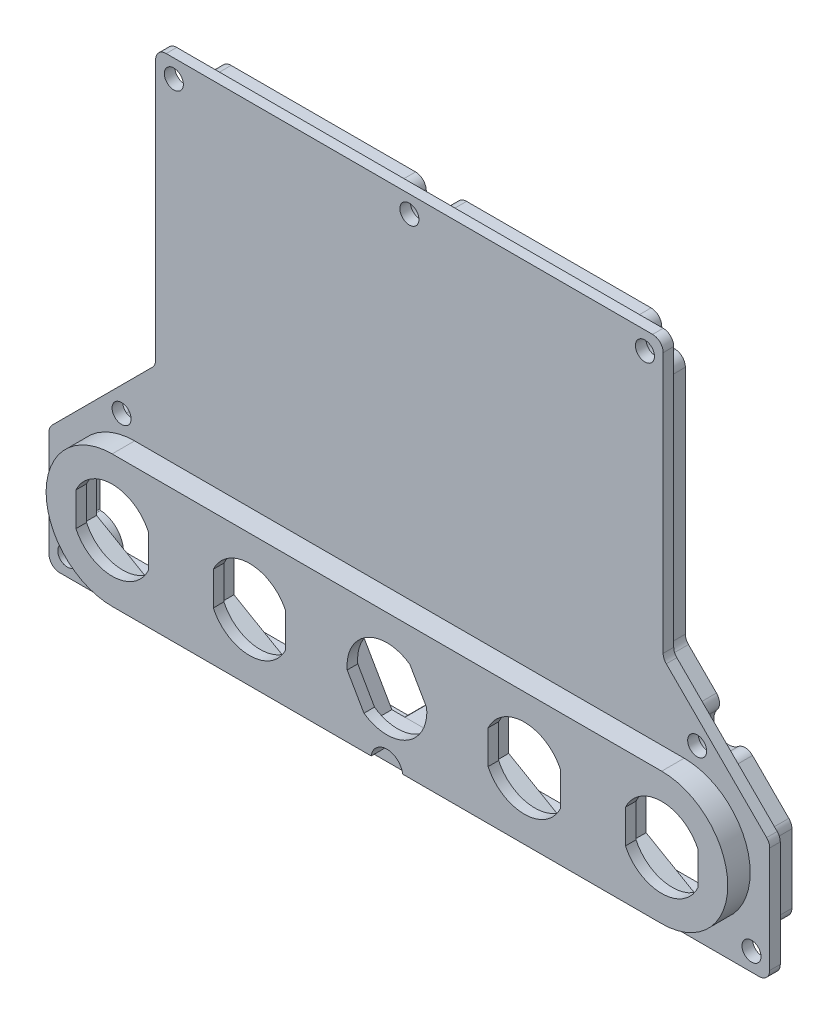
SolidWorks part; units mm, degrees
note: The reader was unsure of these and kept them because the rebuilt part matched: shared geometry of "Sketch1<5>".
ref_plane "Front Plane" through (0, 0, 0) normal (0, 0, 1) x (1, 0, 0)
ref_plane "Top Plane" through (0, 0, 0) normal (0, 1, 0) x (1, 0, 0)
ref_plane "Right Plane" through (0, 0, 0) normal (1, 0, 0) x (0, 0, -1)
sketch "Sketch1" plane through (0, 0, 0) normal (0, 0, 1) x (1, 0, 0)
  line L0 (104.5513, -101.1583) -> (95.5513, -95.9622) construction
  line L1 (113.5513, -95.9622) -> (104.5513, -101.1583) construction
  line L2 (113.5513, -85.5699) -> (113.5513, -95.9622) construction
  line L3 (104.5513, -80.3737) -> (113.5513, -85.5699) construction
  line L4 (95.5513, -85.5699) -> (104.5513, -80.3737) construction
  line L5 (95.5513, -95.9622) -> (95.5513, -85.5699) construction
  line L6 (69.5513, -95.9622) -> (69.5513, -85.5699) construction
  line L7 (78.5513, -101.1583) -> (69.5513, -95.9622) construction
  line L8 (87.5513, -95.9622) -> (78.5513, -101.1583) construction
  line L9 (87.5513, -85.5699) -> (87.5513, -95.9622) construction
  line L10 (78.5513, -80.3737) -> (87.5513, -85.5699) construction
  line L11 (69.5513, -85.5699) -> (78.5513, -80.3737) construction
  line L12 (35.5513, -95.9622) -> (26.5513, -101.1583) construction
  line L13 (26.5513, -101.1583) -> (17.5513, -95.9622) construction
  line L14 (17.5513, -95.9622) -> (17.5513, -85.5699) construction
  line L15 (17.5513, -85.5699) -> (26.5513, -80.3737) construction
  line L16 (26.5513, -80.3737) -> (35.5513, -85.5699) construction
  line L17 (35.5513, -85.5699) -> (35.5513, -95.9622) construction
  line L18 (47.3575, -81.766) -> (57.7498, -81.766) construction
  line L19 (42.1613, -90.766) -> (47.3575, -81.766) construction
  line L20 (47.3575, -99.766) -> (42.1613, -90.766) construction
  line L21 (57.7498, -99.766) -> (47.3575, -99.766) construction
  line L22 (62.946, -90.766) -> (57.7498, -99.766) construction
  line L23 (57.7498, -81.766) -> (62.946, -90.766) construction
  line L24 (9.5513, -95.9622) -> (0.5513, -101.1583) construction
  line L25 (9.5513, -85.5699) -> (9.5513, -95.9622) construction
  line L26 (0.5513, -80.3737) -> (9.5513, -85.5699) construction
  line L27 (-8.4487, -85.5699) -> (0.5513, -80.3737) construction
  line L28 (-8.4487, -95.9622) -> (-8.4487, -85.5699) construction
  line L29 (0.5513, -101.1583) -> (-8.4487, -95.9622) construction
  line L30 (-15.641, -104.9583) -> (-15.641, -84.8874) construction
  line L31 (-15.0552, -83.4732) -> (3.9406, -64.4774) construction
  line L32 (-13.641, -106.9583) -> (118.7436, -106.9583) construction
  line L33 (120.7436, -104.9583) -> (120.7436, -84.8874) construction
  line L34 (120.1579, -83.4732) -> (101.1671, -64.4824) construction
  line L35 (100.5813, -63.0682) -> (100.5813, -13.7887) construction
  line L36 (98.5813, -11.7887) -> (6.5263, -11.7887) construction
  line L37 (4.5263, -63.0632) -> (4.5263, -13.7887) construction
  line L38 (104.5513, -101.1583) -> (95.5513, -95.9622)
  line L39 (113.5513, -95.9622) -> (104.5513, -101.1583)
  line L40 (113.5513, -85.5699) -> (113.5513, -95.9622)
  line L41 (104.5513, -80.3737) -> (113.5513, -85.5699)
  line L42 (95.5513, -85.5699) -> (104.5513, -80.3737)
  line L43 (95.5513, -95.9622) -> (95.5513, -85.5699)
  line L44 (69.5513, -95.9622) -> (69.5513, -85.5699)
  line L45 (78.5513, -101.1583) -> (69.5513, -95.9622)
  line L46 (87.5513, -95.9622) -> (78.5513, -101.1583)
  line L47 (87.5513, -85.5699) -> (87.5513, -95.9622)
  line L48 (78.5513, -80.3737) -> (87.5513, -85.5699)
  line L49 (69.5513, -85.5699) -> (78.5513, -80.3737)
  line L50 (35.5513, -95.9622) -> (26.5513, -101.1583)
  line L51 (26.5513, -101.1583) -> (17.5513, -95.9622)
  line L52 (17.5513, -95.9622) -> (17.5513, -85.5699)
  line L53 (17.5513, -85.5699) -> (26.5513, -80.3737)
  line L54 (26.5513, -80.3737) -> (35.5513, -85.5699)
  line L55 (35.5513, -85.5699) -> (35.5513, -95.9622)
  line L56 (47.3575, -81.766) -> (57.7498, -81.766)
  line L57 (42.1613, -90.766) -> (47.3575, -81.766)
  line L58 (47.3575, -99.766) -> (42.1613, -90.766)
  line L59 (57.7498, -99.766) -> (50.0072, -99.766)
  line L60 (62.946, -90.766) -> (57.7498, -99.766)
  line L61 (57.7498, -81.766) -> (62.946, -90.766)
  line L62 (9.5513, -95.9622) -> (0.5513, -101.1583)
  line L63 (9.5513, -85.5699) -> (9.5513, -95.9622)
  line L64 (0.5513, -80.3737) -> (9.5513, -85.5699)
  line L65 (-8.4487, -85.5699) -> (0.5513, -80.3737)
  line L66 (-8.4487, -95.9622) -> (-8.4487, -85.5699)
  line L67 (0.5513, -101.1583) -> (-8.4487, -95.9622)
  line L68 (-15.641, -104.9583) -> (-15.641, -84.8874)
  line L69 (-15.0552, -83.4732) -> (3.9406, -64.4774)
  line L70 (-13.641, -106.9583) -> (118.7436, -106.9583)
  line L71 (120.7436, -104.9583) -> (120.7436, -84.8874)
  line L72 (120.1579, -83.4732) -> (101.1671, -64.4824)
  line L73 (100.5813, -63.0682) -> (100.5813, -13.7887)
  line L74 (98.5813, -11.7887) -> (6.5263, -11.7887)
  line L75 (4.5263, -63.0632) -> (4.5263, -13.7887)
  line L76 (47.7297, -13.5887) -> (12.8099, -13.5887) construction
  line L77 (6.3263, -63.8088) -> (6.3263, -20.0723) construction
  line L78 (0.4366, -70.5269) -> (5.7406, -65.223) construction
  line L79 (-13.2552, -84.2187) -> (-6.3857, -77.3493) construction
  line L80 (-13.841, -85.633) -> (-13.841, -98.6778) construction
  line L81 (-7.3604, -105.1583) -> (47.7272, -105.1583) construction
  line L82 (57.3755, -105.1583) -> (112.4601, -105.1583) construction
  line L83 (118.9436, -98.6748) -> (118.9436, -85.633) construction
  line L84 (118.3579, -84.2187) -> (111.4884, -77.3493) construction
  line L85 (104.666, -70.5269) -> (99.3671, -65.228) construction
  line L86 (98.7813, -63.8138) -> (98.7813, -20.0723) construction
  line L87 (92.2978, -13.5887) -> (57.378, -13.5887) construction
  line L88 (47.7297, -13.5887) -> (12.8099, -13.5887)
  line L89 (6.3263, -63.8088) -> (6.3263, -20.0723)
  line L90 (0.4366, -70.5269) -> (5.7406, -65.223)
  line L91 (-13.2552, -84.2187) -> (-6.3857, -77.3493)
  line L92 (-13.841, -85.633) -> (-13.841, -98.6778)
  line L93 (-7.3604, -105.1583) -> (47.7272, -105.1583)
  line L94 (57.3755, -105.1583) -> (112.4601, -105.1583)
  line L95 (118.9436, -98.6748) -> (118.9436, -85.633)
  line L96 (118.3579, -84.2187) -> (111.4884, -77.3493)
  line L97 (104.666, -70.5269) -> (99.3671, -65.228)
  line L98 (98.7813, -63.8138) -> (98.7813, -20.0723)
  line L99 (92.2978, -13.5887) -> (57.378, -13.5887)
  line L100 (78.4413, -58.6937) -> (10.3263, -58.6937) construction
  line L101 (78.4413, -34.5887) -> (10.3263, -34.5887) construction
  line L102 (98.7813, -58.6937) -> (6.3263, -58.6937) construction
  line L103 (98.7813, -34.5887) -> (6.3263, -34.5887) construction
  line L104 (96.9813, -34.0887) -> (8.1263, -34.0887)
  line L105 (96.9813, -59.1937) -> (8.1263, -59.1937)
  line L106 (96.9813, -32.2887) -> (8.1263, -32.2887)
  line L107 (96.9813, -60.9937) -> (8.1263, -60.9937)
  line L108 (47.7297, -15.3887) -> (12.8099, -15.3887)
  line L109 (8.1263, -63.8088) -> (8.1263, -60.9937)
  line L110 (1.7094, -71.7997) -> (7.0133, -66.4958)
  line L111 (-11.9824, -85.4915) -> (-5.1129, -78.6221)
  line L112 (-12.041, -85.633) -> (-12.041, -98.6778)
  line L113 (-7.3604, -103.3583) -> (47.7272, -103.3583)
  line L114 (57.3755, -103.3583) -> (112.4601, -103.3583)
  line L115 (117.1436, -98.6748) -> (117.1436, -85.633)
  line L116 (117.0851, -85.4915) -> (110.2156, -78.6221)
  line L117 (103.3932, -71.7997) -> (98.0943, -66.5008)
  line L118 (96.9813, -63.8138) -> (96.9813, -60.9937)
  line L119 (92.2978, -15.3887) -> (57.378, -15.3887)
  line L120 (49.7165, -99.9724) -> (55.3862, -99.9724)
  line L121 (47.3575, -99.766) -> (50.0072, -99.766)
  line L122 (8.1263, -59.1937) -> (8.1263, -34.0887)
  line L123 (98.7813, -59.1937) -> (6.3263, -59.1937) construction
  line L124 (98.7813, -60.9937) -> (6.3263, -60.9937) construction
  line L125 (96.9813, -59.1937) -> (96.9813, -34.0887)
  line L126 (8.1263, -63.8088) -> (8.1263, -20.0723) construction
  line L127 (96.9813, -32.2887) -> (96.9813, -20.0723)
  line L128 (96.9813, -63.8138) -> (96.9813, -20.0723) construction
  line L129 (98.7813, -32.2887) -> (6.3263, -32.2887) construction
  line L130 (8.1263, -32.2887) -> (8.1263, -20.0723)
  line L131 (98.7813, -34.0887) -> (6.3263, -34.0887) construction
  line L132 (9.7513, -85.4544) -> (9.7513, -96.0776)
  line L133 (9.7513, -96.0776) -> (0.5513, -101.3893)
  line L134 (0.5513, -101.3893) -> (-8.6487, -96.0776)
  line L135 (-8.6487, -96.0776) -> (-8.6487, -85.4544)
  line L136 (-8.6487, -85.4544) -> (0.5513, -80.1428)
  line L137 (0.5513, -80.1428) -> (9.7513, -85.4544)
  line L138 (17.3513, -96.0776) -> (17.3513, -85.4544)
  line L139 (17.3513, -85.4544) -> (26.5513, -80.1428)
  line L140 (26.5513, -80.1428) -> (35.7513, -85.4544)
  line L141 (35.7513, -85.4544) -> (35.7513, -96.0776)
  line L142 (35.7513, -96.0776) -> (26.5513, -101.3893)
  line L143 (26.5513, -101.3893) -> (17.3513, -96.0776)
  line L144 (63.1769, -90.766) -> (57.8653, -99.966)
  line L145 (57.8653, -99.966) -> (50.0072, -99.966)
  line L146 (47.242, -99.966) -> (50.0072, -99.966)
  line L147 (47.242, -99.966) -> (41.9304, -90.766)
  line L148 (41.9304, -90.766) -> (47.242, -81.566)
  line L149 (47.242, -81.566) -> (57.8653, -81.566)
  line L150 (57.8653, -81.566) -> (63.1769, -90.766)
  line L151 (69.3513, -96.0776) -> (69.3513, -85.4544)
  line L152 (69.3513, -85.4544) -> (78.5513, -80.1428)
  line L153 (78.5513, -80.1428) -> (87.7513, -85.4544)
  line L154 (87.7513, -85.4544) -> (87.7513, -96.0776)
  line L155 (87.7513, -96.0776) -> (78.5513, -101.3893)
  line L156 (78.5513, -101.3893) -> (69.3513, -96.0776)
  line L157 (113.7513, -85.4544) -> (113.7513, -96.0776)
  line L158 (113.7513, -96.0776) -> (104.5513, -101.3893)
  line L159 (104.5513, -101.3893) -> (95.3513, -96.0776)
  line L160 (95.3513, -96.0776) -> (95.3513, -85.4544)
  line L161 (95.3513, -85.4544) -> (104.5513, -80.1428)
  line L162 (104.5513, -80.1428) -> (113.7513, -85.4544)
  arc A0 (-15.641, -104.9583) -> (-13.641, -106.9583) centre (-13.641, -104.9583) ccw construction
  arc A1 (-15.0552, -83.4732) -> (-15.641, -84.8874) centre (-13.641, -84.8874) ccw construction
  arc A2 (3.9406, -64.4774) -> (4.5263, -63.0632) centre (2.5263, -63.0632) ccw construction
  arc A3 (118.7436, -106.9583) -> (120.7436, -104.9583) centre (118.7436, -104.9583) ccw construction
  arc A4 (120.7436, -84.8874) -> (120.1579, -83.4732) centre (118.7436, -84.8874) ccw construction
  arc A5 (100.5813, -63.0682) -> (101.1671, -64.4824) centre (102.5813, -63.0682) ccw construction
  arc A6 (100.5813, -13.7887) -> (98.5813, -11.7887) centre (98.5813, -13.7887) ccw construction
  arc A7 (6.5263, -11.7887) -> (4.5263, -13.7887) centre (6.5263, -13.7887) ccw construction
  arc A8 (-15.641, -104.9583) -> (-13.641, -106.9583) centre (-13.641, -104.9583) ccw
  arc A9 (-15.0552, -83.4732) -> (-15.641, -84.8874) centre (-13.641, -84.8874) ccw
  arc A10 (3.9406, -64.4774) -> (4.5263, -63.0632) centre (2.5263, -63.0632) ccw
  arc A11 (118.7436, -106.9583) -> (120.7436, -104.9583) centre (118.7436, -104.9583) ccw
  arc A12 (120.7436, -84.8874) -> (120.1579, -83.4732) centre (118.7436, -84.8874) ccw
  arc A13 (100.5813, -63.0682) -> (101.1671, -64.4824) centre (102.5813, -63.0682) ccw
  arc A14 (100.5813, -13.7887) -> (98.5813, -11.7887) centre (98.5813, -13.7887) ccw
  arc A15 (6.5263, -11.7887) -> (4.5263, -13.7887) centre (6.5263, -13.7887) ccw
  circle A16 centre (7.9728, -15.2352) radius 1.8
  circle A17 centre (52.5538, -15.0887) radius 1.8
  circle A18 centre (97.1349, -15.2352) radius 1.8
  circle A19 centre (107.0166, -74.9988) radius 1.8
  circle A20 centre (117.2972, -103.5119) radius 1.8
  circle A21 centre (52.5513, -103.6583) radius 1.8
  circle A22 centre (-12.1957, -103.5131) radius 1.8
  circle A23 centre (-1.9139, -74.9988) radius 1.8
  arc A24 (57.378, -13.5887) -> (55.3887, -15.3825) centre (57.378, -15.5887) ccw construction
  arc A25 (49.719, -15.3825) -> (55.3887, -15.3825) centre (52.5538, -15.0887) ccw construction
  arc A26 (49.719, -15.3825) -> (47.7297, -13.5887) centre (47.7297, -15.5887) ccw construction
  arc A27 (12.8099, -13.5887) -> (10.8152, -15.4429) centre (12.8099, -15.5887) ccw construction
  arc A28 (8.1805, -18.0776) -> (10.8152, -15.4429) centre (7.9728, -15.2352) ccw construction
  arc A29 (8.1805, -18.0776) -> (6.3263, -20.0723) centre (8.3263, -20.0723) ccw construction
  arc A30 (5.7406, -65.223) -> (6.3263, -63.8088) centre (4.3263, -63.8088) ccw construction
  arc A31 (0.4366, -70.5269) -> (0.2984, -73.202) centre (1.8509, -71.9411) ccw construction
  arc A32 (-3.7106, -77.211) -> (0.2984, -73.202) centre (-1.9139, -74.9988) ccw construction
  arc A33 (-3.7106, -77.211) -> (-6.3857, -77.3493) centre (-4.9715, -78.7635) ccw construction
  arc A34 (-13.2552, -84.2187) -> (-13.841, -85.633) centre (-11.841, -85.633) ccw construction
  arc A35 (-13.841, -98.6778) -> (-11.9873, -100.6724) centre (-11.841, -98.6778) ccw construction
  arc A36 (-9.355, -103.3047) -> (-11.9873, -100.6724) centre (-12.1957, -103.5131) ccw construction
  arc A37 (-9.355, -103.3047) -> (-7.3604, -105.1583) centre (-7.3604, -103.1583) ccw construction
  arc A38 (47.7272, -105.1583) -> (49.7165, -103.3645) centre (47.7272, -103.1583) ccw construction
  arc A39 (55.3862, -103.3645) -> (49.7165, -103.3645) centre (52.5513, -103.6583) ccw construction
  arc A40 (55.3862, -103.3645) -> (57.3755, -105.1583) centre (57.3755, -103.1583) ccw construction
  arc A41 (112.4601, -105.1583) -> (114.4548, -103.3041) centre (112.4601, -103.1583) ccw construction
  arc A42 (117.0894, -100.6695) -> (114.4548, -103.3041) centre (117.2972, -103.5119) ccw construction
  arc A43 (117.0894, -100.6695) -> (118.9436, -98.6748) centre (116.9436, -98.6748) ccw construction
  arc A44 (118.9436, -85.633) -> (118.3579, -84.2187) centre (116.9436, -85.633) ccw construction
  arc A45 (111.4884, -77.3493) -> (108.8133, -77.211) centre (110.0742, -78.7635) ccw construction
  arc A46 (104.8043, -73.202) -> (108.8133, -77.211) centre (107.0166, -74.9988) ccw construction
  arc A47 (104.8043, -73.202) -> (104.666, -70.5269) centre (103.2518, -71.9411) ccw construction
  arc A48 (98.7813, -63.8138) -> (99.3671, -65.228) centre (100.7813, -63.8138) ccw construction
  arc A49 (94.2925, -15.4429) -> (92.2978, -13.5887) centre (92.2978, -15.5887) ccw construction
  arc A50 (94.2925, -15.4429) -> (96.9271, -18.0776) centre (97.1349, -15.2352) ccw construction
  arc A51 (98.7813, -20.0723) -> (96.9271, -18.0776) centre (96.7813, -20.0723) ccw construction
  arc A52 (57.378, -13.5887) -> (55.3887, -15.3825) centre (57.378, -15.5887) ccw
  arc A53 (49.719, -15.3825) -> (55.3887, -15.3825) centre (52.5538, -15.0887) ccw
  arc A54 (49.719, -15.3825) -> (47.7297, -13.5887) centre (47.7297, -15.5887) ccw
  arc A55 (12.8099, -13.5887) -> (10.8152, -15.4429) centre (12.8099, -15.5887) ccw
  arc A56 (8.1805, -18.0776) -> (10.8152, -15.4429) centre (7.9728, -15.2352) ccw
  arc A57 (8.1805, -18.0776) -> (6.3263, -20.0723) centre (8.3263, -20.0723) ccw
  arc A58 (5.7406, -65.223) -> (6.3263, -63.8088) centre (4.3263, -63.8088) ccw
  arc A59 (0.4366, -70.5269) -> (0.2984, -73.202) centre (1.8509, -71.9411) ccw
  arc A60 (-3.7106, -77.211) -> (0.2984, -73.202) centre (-1.9139, -74.9988) ccw
  arc A61 (-3.7106, -77.211) -> (-6.3857, -77.3493) centre (-4.9715, -78.7635) ccw
  arc A62 (-13.2552, -84.2187) -> (-13.841, -85.633) centre (-11.841, -85.633) ccw
  arc A63 (-13.841, -98.6778) -> (-11.9873, -100.6724) centre (-11.841, -98.6778) ccw
  arc A64 (-9.355, -103.3047) -> (-11.9873, -100.6724) centre (-12.1957, -103.5131) ccw
  arc A65 (-9.355, -103.3047) -> (-7.3604, -105.1583) centre (-7.3604, -103.1583) ccw
  arc A66 (47.7272, -105.1583) -> (49.7165, -103.3645) centre (47.7272, -103.1583) ccw
  arc A67 (55.3862, -103.3645) -> (49.7165, -103.3645) centre (52.5513, -103.6583) ccw
  arc A68 (55.3862, -103.3645) -> (57.3755, -105.1583) centre (57.3755, -103.1583) ccw
  arc A69 (112.4601, -105.1583) -> (114.4548, -103.3041) centre (112.4601, -103.1583) ccw
  arc A70 (117.0894, -100.6695) -> (114.4548, -103.3041) centre (117.2972, -103.5119) ccw
  arc A71 (117.0894, -100.6695) -> (118.9436, -98.6748) centre (116.9436, -98.6748) ccw
  arc A72 (118.9436, -85.633) -> (118.3579, -84.2187) centre (116.9436, -85.633) ccw
  arc A73 (111.4884, -77.3493) -> (108.8133, -77.211) centre (110.0742, -78.7635) ccw
  arc A74 (104.8043, -73.202) -> (108.8133, -77.211) centre (107.0166, -74.9988) ccw
  arc A75 (104.8043, -73.202) -> (104.666, -70.5269) centre (103.2518, -71.9411) ccw
  arc A76 (98.7813, -63.8138) -> (99.3671, -65.228) centre (100.7813, -63.8138) ccw
  arc A77 (94.2925, -15.4429) -> (92.2978, -13.5887) centre (92.2978, -15.5887) ccw
  arc A78 (94.2925, -15.4429) -> (96.9271, -18.0776) centre (97.1349, -15.2352) ccw
  arc A79 (98.7813, -20.0723) -> (96.9271, -18.0776) centre (96.7813, -20.0723) ccw
  arc A80 (12.8099, -15.3887) -> (12.6104, -15.5741) centre (12.8099, -15.5887) ccw
  arc A81 (8.3118, -19.8728) -> (12.6104, -15.5741) centre (7.9728, -15.2352) ccw
  arc A82 (8.3118, -19.8728) -> (8.1263, -20.0723) centre (8.3263, -20.0723) ccw
  arc A83 (7.0133, -66.4958) -> (8.1263, -63.8088) centre (4.3263, -63.8088) ccw
  arc A84 (1.7094, -71.7997) -> (1.6956, -72.0672) centre (1.8509, -71.9411) ccw
  arc A85 (-4.8454, -78.6083) -> (1.6956, -72.0672) centre (-1.9139, -74.9988) ccw
  arc A86 (-4.8454, -78.6083) -> (-5.1129, -78.6221) centre (-4.9715, -78.7635) ccw
  arc A87 (-11.9824, -85.4915) -> (-12.041, -85.633) centre (-11.841, -85.633) ccw
  arc A88 (-12.041, -98.6778) -> (-11.8556, -98.8772) centre (-11.841, -98.6778) ccw
  arc A89 (-7.5599, -103.173) -> (-11.8556, -98.8772) centre (-12.1957, -103.5131) ccw
  arc A90 (-7.5599, -103.173) -> (-7.3604, -103.3583) centre (-7.3604, -103.1583) ccw
  arc A91 (47.7272, -103.3583) -> (47.9261, -103.1789) centre (47.7272, -103.1583) ccw
  arc A92 (57.1766, -103.1789) -> (55.3862, -99.9724) centre (52.5513, -103.6583) ccw
  arc A93 (57.1766, -103.1789) -> (57.3755, -103.3583) centre (57.3755, -103.1583) ccw
  arc A94 (112.4601, -103.3583) -> (112.6596, -103.1729) centre (112.4601, -103.1583) ccw
  arc A95 (116.9582, -98.8742) -> (112.6596, -103.1729) centre (117.2972, -103.5119) ccw
  arc A96 (116.9582, -98.8742) -> (117.1436, -98.6748) centre (116.9436, -98.6748) ccw
  arc A97 (117.1436, -85.633) -> (117.0851, -85.4915) centre (116.9436, -85.633) ccw
  arc A98 (110.2156, -78.6221) -> (109.9481, -78.6083) centre (110.0742, -78.7635) ccw
  arc A99 (103.4071, -72.0672) -> (109.9481, -78.6083) centre (107.0166, -74.9988) ccw
  arc A100 (103.4071, -72.0672) -> (103.3932, -71.7997) centre (103.2518, -71.9411) ccw
  arc A101 (96.9813, -63.8138) -> (98.0943, -66.5008) centre (100.7813, -63.8138) ccw
  arc A102 (96.9813, -20.0723) -> (96.7959, -19.8728) centre (96.7813, -20.0723) ccw
  arc A103 (92.4973, -15.5741) -> (96.7959, -19.8728) centre (97.1349, -15.2352) ccw
  arc A104 (92.4973, -15.5741) -> (92.2978, -15.3887) centre (92.2978, -15.5887) ccw
  arc A105 (57.378, -15.3887) -> (57.1791, -15.5681) centre (57.378, -15.5887) ccw
  arc A106 (47.9286, -15.5681) -> (57.1791, -15.5681) centre (52.5538, -15.0887) ccw
  arc A107 (47.9286, -15.5681) -> (47.7297, -15.3887) centre (47.7297, -15.5887) ccw
  arc A108 (49.7165, -99.9724) -> (47.9261, -103.1789) centre (52.5513, -103.6583) ccw
  arc A110 (57.1766, -103.1789) -> (47.9261, -103.1789) centre (52.5513, -103.6583) ccw construction
  dimension "D1" = 0.5
  dimension "D2" = 0.5
  dimension "D3" = 1.8
  dimension "D4" = 1.8
  dimension "D5" = 1.8
  dimension "D6" = 0.2
extrude "Boss-Extrude1" add sketch "Sketch1" against normal blind 4 contours L98 A79 A78 A77 L99 A52 A53 A54 L88 A55 A56 A57 L89 A58 L90 A59 A60 A61 L91 A62 L92 A63 A64 A65 L93 A66 A67 A68 L94 A69 A70 A71 L95 A72 L96 A73 A74 A75 L97 A76 L125 L105 L122 L104 A107 A106 A105 L119 A104
extrude "Boss-Extrude3" add sketch "Sketch1<5>" along normal blind 2 contours L98 A79 A78 A77 L99 A52 A53 A54 L88 A55 A56 A57 L89 A58 L90 A59 A60 A61 L91 A62 L92 A63 A64 A65 L93 A66 A67 A68 L94 A69 A70 A71 L95 A72 L96 A73 A74 A75 L97 A76 L125 L105 L122 L104 A107 A106 A105 L119 A104 | L74 A15 L75 A10 L69 A9 L68 A8 L70 A11 L71 A12 L72 A13 L73 A14 A79 L98 A76 L97 A75 A74 A73 L96 A72 L95 A71 A70 A69 L94 A68 A67 A66 L93 A65 A64 A63 L92 A62 L91 A61 A60 A59 L90 A58 L89 A57 A56 A55 L88 | A108 L120 A92 A93 L114 A94 A95 A96 L115 A97 L116 A98 A99 A100 L117 A101 L118 L107 L109 A83 L110 A84 A85 A86 L111 A87 L112 A88 A89 A90 L113 A91 L121 L58 L57 L56 L61 L60 L59 L38 L43 L42 L41 L40 L39 L44 L49 L48 | L105 L125 L104 L122 | A106 A107 L108 A80 A81 A82 L130 L106 L127 A102 A103 A104 L119 A105
sketch "Sketch1<5>" plane through (0, 0, 0) normal (0, 0, 1) x (1, 0, 0) same geometry as "Sketch1"
sketch "Sketch2" plane through (0, 0, 2) normal (0, 0, 1) x (1, 0, 0)
  line L0 (0.5513, -78.266) -> (104.5513, -78.266)
  line L1 (0.5513, -103.266) -> (49.5771, -103.266)
  line L2 (55.5256, -103.266) -> (104.5513, -103.266)
  line L3 (-8.6487, -85.4544) -> (0.5513, -80.1428) construction
  line L4 (-8.6487, -85.4544) -> (0.5513, -80.1428)
  line L5 (113.7513, -96.0776) -> (104.5513, -101.3893) construction
  line L6 (113.7513, -85.4544) -> (113.7513, -96.0776) construction
  line L7 (104.5513, -80.1428) -> (113.7513, -85.4544) construction
  line L8 (104.5513, -101.3893) -> (95.3513, -96.0776) construction
  line L9 (95.3513, -96.0776) -> (95.3513, -85.4544) construction
  line L10 (95.3513, -85.4544) -> (104.5513, -80.1428) construction
  line L11 (87.7513, -96.0776) -> (78.5513, -101.3893) construction
  line L12 (87.7513, -85.4544) -> (87.7513, -96.0776) construction
  line L13 (78.5513, -80.1428) -> (87.7513, -85.4544) construction
  line L14 (78.5513, -101.3893) -> (69.3513, -96.0776) construction
  line L15 (69.3513, -85.4544) -> (78.5513, -80.1428) construction
  line L16 (69.3513, -96.0776) -> (69.3513, -85.4544) construction
  line L17 (47.242, -81.566) -> (57.8653, -81.566) construction
  line L18 (57.8653, -81.566) -> (63.1769, -90.766) construction
  line L19 (63.1769, -90.766) -> (57.8653, -99.966) construction
  line L20 (57.8653, -99.966) -> (47.242, -99.966) construction
  line L21 (47.242, -99.966) -> (41.9304, -90.766) construction
  line L22 (41.9304, -90.766) -> (47.242, -81.566) construction
  line L23 (26.5513, -80.1428) -> (35.7513, -85.4544) construction
  line L24 (35.7513, -85.4544) -> (35.7513, -96.0776) construction
  line L25 (35.7513, -96.0776) -> (26.5513, -101.3893) construction
  line L26 (26.5513, -101.3893) -> (17.3513, -96.0776) construction
  line L27 (17.3513, -96.0776) -> (17.3513, -85.4544) construction
  line L28 (17.3513, -85.4544) -> (26.5513, -80.1428) construction
  line L29 (0.5513, -80.1428) -> (9.7513, -85.4544) construction
  line L30 (9.7513, -85.4544) -> (9.7513, -96.0776) construction
  line L31 (9.7513, -96.0776) -> (0.5513, -101.3893) construction
  line L32 (0.5513, -101.3893) -> (-8.6487, -96.0776) construction
  line L33 (-8.6487, -96.0776) -> (-8.6487, -85.4544) construction
  line L34 (113.7513, -96.0776) -> (104.5513, -101.3893)
  line L35 (113.7513, -85.4544) -> (113.7513, -96.0776)
  line L36 (104.5513, -80.1428) -> (113.7513, -85.4544)
  line L37 (104.5513, -101.3893) -> (95.3513, -96.0776)
  line L38 (95.3513, -96.0776) -> (95.3513, -85.4544)
  line L39 (95.3513, -85.4544) -> (104.5513, -80.1428)
  line L40 (87.7513, -96.0776) -> (78.5513, -101.3893)
  line L41 (87.7513, -85.4544) -> (87.7513, -96.0776)
  line L42 (78.5513, -80.1428) -> (87.7513, -85.4544)
  line L43 (78.5513, -101.3893) -> (69.3513, -96.0776)
  line L44 (69.3513, -85.4544) -> (78.5513, -80.1428)
  line L45 (69.3513, -96.0776) -> (69.3513, -85.4544)
  line L46 (47.242, -81.566) -> (57.8653, -81.566)
  line L47 (57.8653, -81.566) -> (63.1769, -90.766)
  line L48 (63.1769, -90.766) -> (57.8653, -99.966)
  line L49 (57.8653, -99.966) -> (47.242, -99.966)
  line L50 (47.242, -99.966) -> (41.9304, -90.766)
  line L51 (41.9304, -90.766) -> (47.242, -81.566)
  line L52 (26.5513, -80.1428) -> (35.7513, -85.4544)
  line L53 (35.7513, -85.4544) -> (35.7513, -96.0776)
  line L54 (35.7513, -96.0776) -> (26.5513, -101.3893)
  line L55 (26.5513, -101.3893) -> (17.3513, -96.0776)
  line L56 (17.3513, -96.0776) -> (17.3513, -85.4544)
  line L57 (17.3513, -85.4544) -> (26.5513, -80.1428)
  line L58 (0.5513, -80.1428) -> (9.7513, -85.4544)
  line L59 (9.7513, -85.4544) -> (9.7513, -96.0776)
  line L60 (9.7513, -96.0776) -> (0.5513, -101.3893)
  line L61 (0.5513, -101.3893) -> (-8.6487, -96.0776)
  line L62 (-8.6487, -96.0776) -> (-8.6487, -85.4544)
  arc A0 (0.5513, -78.266) -> (0.5513, -103.266) centre (0.5513, -90.766) ccw
  arc A1 (104.5513, -103.266) -> (104.5513, -78.266) centre (104.5513, -90.766) ccw
  arc A2 (55.5256, -103.266) -> (49.5771, -103.266) centre (52.5513, -103.6583) ccw
extrude "Boss-Extrude4" add sketch "Sketch2" along normal blind 2.25 contours A2 L2 A1 L0 A0 L1 L38 L39 L36 L35 L34 L37 L43 L45 L44 L42 L41 L40 L50 L51 L46 L47 L48 L49 L56 L57 L52 L53 L54 L55 L61 L62 L4 L58 L59 L60
sketch "Sketch3" plane through (0, 0, 4.25) normal (0, 0, 1) x (1, 0, 0)
  line L0 (33.3013, -90.766) -> (33.3013, -93.9188) construction
  line L1 (7.3013, -90.766) -> (7.3013, -93.9188) construction
  line L2 (-6.1987, -90.766) -> (-6.1987, -93.9188) construction
  line L3 (19.8013, -90.766) -> (19.8013, -93.9188) construction
  line L4 (19.8013, -90.766) -> (19.8013, -87.6132) construction
  line L5 (33.3013, -90.766) -> (33.3013, -87.6132) construction
  line L6 (7.3013, -90.766) -> (7.3013, -87.6132) construction
  line L7 (-6.1987, -90.766) -> (-6.1987, -87.6132) construction
  line L8 (33.3013, -90.766) -> (33.3013, -93.9188)
  line L9 (7.3013, -90.766) -> (7.3013, -93.9188)
  line L10 (-6.1987, -90.766) -> (-6.1987, -93.9188)
  line L11 (19.8013, -90.766) -> (19.8013, -93.9188)
  line L12 (19.8013, -90.766) -> (19.8013, -87.6132)
  line L13 (33.3013, -90.766) -> (33.3013, -87.6132)
  line L14 (7.3013, -90.766) -> (7.3013, -87.6132)
  line L15 (-6.1987, -90.766) -> (-6.1987, -87.6132)
  line L16 (97.8013, -90.766) -> (97.8013, -93.9188) construction
  line L17 (97.8013, -90.766) -> (97.8013, -87.6132) construction
  line L18 (111.3013, -90.766) -> (111.3013, -93.9188) construction
  line L19 (111.3013, -90.766) -> (111.3013, -87.6132) construction
  line L20 (85.3013, -90.766) -> (85.3013, -93.9188) construction
  line L21 (85.3013, -90.766) -> (85.3013, -87.6132) construction
  line L22 (71.8013, -90.766) -> (71.8013, -93.9188) construction
  line L23 (71.8013, -90.766) -> (71.8013, -87.6132) construction
  line L24 (46.708, -94.141) -> (48.2844, -96.8714) construction
  line L25 (46.708, -94.141) -> (45.1316, -91.4106) construction
  line L26 (58.3993, -87.391) -> (59.9757, -90.1214) construction
  line L27 (58.3993, -87.391) -> (56.8229, -84.6606) construction
  line L28 (97.8013, -90.766) -> (97.8013, -93.9188)
  line L29 (97.8013, -90.766) -> (97.8013, -87.6132)
  line L30 (111.3013, -90.766) -> (111.3013, -93.9188)
  line L31 (111.3013, -90.766) -> (111.3013, -87.6132)
  line L32 (85.3013, -90.766) -> (85.3013, -93.9188)
  line L33 (85.3013, -90.766) -> (85.3013, -87.6132)
  line L34 (71.8013, -90.766) -> (71.8013, -93.9188)
  line L35 (71.8013, -90.766) -> (71.8013, -87.6132)
  line L36 (46.708, -94.141) -> (48.2844, -96.8714)
  line L37 (46.708, -94.141) -> (45.1316, -91.4106)
  line L38 (58.3993, -87.391) -> (59.9757, -90.1214)
  line L39 (58.3993, -87.391) -> (56.8229, -84.6606)
  line L40 (7.4013, -90.766) -> (7.4013, -93.9409)
  line L41 (7.4013, -90.766) -> (7.4013, -87.5911)
  line L42 (-6.2987, -90.766) -> (-6.2987, -87.5911)
  line L43 (-6.2987, -90.766) -> (-6.2987, -93.9409)
  line L44 (33.4013, -90.766) -> (33.4013, -93.9409)
  line L45 (33.4013, -90.766) -> (33.4013, -87.5911)
  line L46 (19.7013, -90.766) -> (19.7013, -87.5911)
  line L47 (19.7013, -90.766) -> (19.7013, -93.9409)
  line L48 (46.6214, -94.191) -> (45.0339, -91.4415)
  line L49 (46.6214, -94.191) -> (48.2088, -96.9406)
  line L50 (58.4859, -87.341) -> (60.0734, -90.0906)
  line L51 (58.4859, -87.341) -> (56.8985, -84.5915)
  line L52 (85.4013, -90.766) -> (85.4013, -93.9409)
  line L53 (85.4013, -90.766) -> (85.4013, -87.5911)
  line L54 (71.7013, -90.766) -> (71.7013, -87.5911)
  line L55 (71.7013, -90.766) -> (71.7013, -93.9409)
  line L56 (111.4013, -90.766) -> (111.4013, -93.9409)
  line L57 (111.4013, -90.766) -> (111.4013, -87.5911)
  line L58 (97.7013, -90.766) -> (97.7013, -87.5911)
  line L59 (97.7013, -90.766) -> (97.7013, -93.9409)
  line L60 (55.5256, -103.266) -> (104.5513, -103.266) construction
  line L61 (0.5513, -78.266) -> (104.5513, -78.266) construction
  line L62 (0.5513, -103.266) -> (49.5771, -103.266) construction
  line L63 (55.5256, -103.266) -> (104.5513, -103.266)
  line L64 (0.5513, -78.266) -> (104.5513, -78.266)
  line L65 (0.5513, -103.266) -> (49.5771, -103.266)
  arc A0 (-6.1987, -93.9188) -> (7.3013, -93.9188) centre (0.5513, -90.766) ccw construction
  arc A1 (19.8013, -93.9188) -> (33.3013, -93.9188) centre (26.5513, -90.766) ccw construction
  arc A2 (33.3013, -87.6132) -> (19.8013, -87.6132) centre (26.5513, -90.766) ccw construction
  arc A3 (7.3013, -87.6132) -> (-6.1987, -87.6132) centre (0.5513, -90.766) ccw construction
  arc A4 (-6.1987, -93.9188) -> (7.3013, -93.9188) centre (0.5513, -90.766) ccw
  arc A5 (19.8013, -93.9188) -> (33.3013, -93.9188) centre (26.5513, -90.766) ccw
  arc A6 (33.3013, -87.6132) -> (19.8013, -87.6132) centre (26.5513, -90.766) ccw
  arc A7 (7.3013, -87.6132) -> (-6.1987, -87.6132) centre (0.5513, -90.766) ccw
  arc A8 (97.8013, -93.9188) -> (111.3013, -93.9188) centre (104.5513, -90.766) ccw construction
  arc A9 (111.3013, -87.6132) -> (97.8013, -87.6132) centre (104.5513, -90.766) ccw construction
  arc A10 (71.8013, -93.9188) -> (85.3013, -93.9188) centre (78.5513, -90.766) ccw construction
  arc A11 (85.3013, -87.6132) -> (71.8013, -87.6132) centre (78.5513, -90.766) ccw construction
  arc A12 (56.8229, -84.6606) -> (45.1316, -91.4106) centre (52.5536, -90.766) ccw construction
  arc A13 (48.2844, -96.8714) -> (59.9757, -90.1214) centre (52.5536, -90.766) ccw construction
  arc A14 (97.8013, -93.9188) -> (111.3013, -93.9188) centre (104.5513, -90.766) ccw
  arc A15 (111.3013, -87.6132) -> (97.8013, -87.6132) centre (104.5513, -90.766) ccw
  arc A16 (71.8013, -93.9188) -> (85.3013, -93.9188) centre (78.5513, -90.766) ccw
  arc A17 (85.3013, -87.6132) -> (71.8013, -87.6132) centre (78.5513, -90.766) ccw
  arc A18 (56.8229, -84.6606) -> (45.1316, -91.4106) centre (52.5536, -90.766) ccw
  arc A19 (48.2844, -96.8714) -> (59.9757, -90.1214) centre (52.5536, -90.766) ccw
  arc A20 (-6.2987, -93.9409) -> (7.4013, -93.9409) centre (0.5513, -90.766) ccw
  arc A21 (7.4013, -87.5911) -> (-6.2987, -87.5911) centre (0.5513, -90.766) ccw
  arc A22 (19.7013, -93.9409) -> (33.4013, -93.9409) centre (26.5513, -90.766) ccw
  arc A23 (33.4013, -87.5911) -> (19.7013, -87.5911) centre (26.5513, -90.766) ccw
  arc A24 (56.8985, -84.5915) -> (45.0339, -91.4415) centre (52.5536, -90.766) ccw
  arc A25 (48.2088, -96.9406) -> (60.0734, -90.0906) centre (52.5536, -90.766) ccw
  arc A26 (71.7013, -93.9409) -> (85.4013, -93.9409) centre (78.5513, -90.766) ccw
  arc A27 (85.4013, -87.5911) -> (71.7013, -87.5911) centre (78.5513, -90.766) ccw
  arc A28 (97.7013, -93.9409) -> (111.4013, -93.9409) centre (104.5513, -90.766) ccw
  arc A29 (111.4013, -87.5911) -> (97.7013, -87.5911) centre (104.5513, -90.766) ccw
  arc A30 (104.5513, -103.266) -> (104.5513, -78.266) centre (104.5513, -90.766) ccw construction
  arc A31 (55.5256, -103.266) -> (49.5771, -103.266) centre (52.5513, -103.6583) ccw construction
  arc A32 (0.5513, -78.266) -> (0.5513, -103.266) centre (0.5513, -90.766) ccw construction
  arc A33 (104.5513, -103.266) -> (104.5513, -78.266) centre (104.5513, -90.766) ccw
  arc A34 (55.5256, -103.266) -> (49.5771, -103.266) centre (52.5513, -103.6583) ccw
  arc A35 (0.5513, -78.266) -> (0.5513, -103.266) centre (0.5513, -90.766) ccw
  arc M1 (49.5771, -103.266) -> (55.5256, -103.266) centre (52.5513, -103.6583) cw
  line M2 (55.5256, -103.266) -> (104.5513, -103.266)
  arc M3 (104.5513, -103.266) -> (104.5513, -78.266) centre (104.5513, -90.766) ccw
  line M4 (104.5513, -78.266) -> (0.5513, -78.266)
  arc M5 (0.5513, -78.266) -> (0.5513, -103.266) centre (0.5513, -90.766) ccw
  line M6 (0.5513, -103.266) -> (49.5771, -103.266)
  line M7 (95.3513, -96.0776) -> (95.3513, -85.4544)
  line M8 (95.3513, -85.4544) -> (104.5513, -80.1428)
  line M9 (104.5513, -80.1428) -> (113.7513, -85.4544)
  line M10 (113.7513, -85.4544) -> (113.7513, -96.0776)
  line M11 (113.7513, -96.0776) -> (104.5513, -101.3893)
  line M12 (104.5513, -101.3893) -> (95.3513, -96.0776)
  line M13 (78.5513, -101.3893) -> (69.3513, -96.0776)
  line M14 (69.3513, -96.0776) -> (69.3513, -85.4544)
  line M15 (69.3513, -85.4544) -> (78.5513, -80.1428)
  line M16 (78.5513, -80.1428) -> (87.7513, -85.4544)
  line M17 (87.7513, -85.4544) -> (87.7513, -96.0776)
  line M18 (87.7513, -96.0776) -> (78.5513, -101.3893)
  line M19 (47.242, -99.966) -> (41.9304, -90.766)
  line M20 (41.9304, -90.766) -> (47.242, -81.566)
  line M21 (47.242, -81.566) -> (57.8653, -81.566)
  line M22 (57.8653, -81.566) -> (63.1769, -90.766)
  line M23 (63.1769, -90.766) -> (57.8653, -99.966)
  line M24 (57.8653, -99.966) -> (47.242, -99.966)
  line M25 (17.3513, -96.0776) -> (17.3513, -85.4544)
  line M26 (17.3513, -85.4544) -> (26.5513, -80.1428)
  line M27 (26.5513, -80.1428) -> (35.7513, -85.4544)
  line M28 (35.7513, -85.4544) -> (35.7513, -96.0776)
  line M29 (35.7513, -96.0776) -> (26.5513, -101.3893)
  line M30 (26.5513, -101.3893) -> (17.3513, -96.0776)
  line M31 (0.5513, -101.3893) -> (-8.6487, -96.0776)
  line M32 (-8.6487, -96.0776) -> (-8.6487, -85.4544)
  line M33 (-8.6487, -85.4544) -> (0.5513, -80.1428)
  line M34 (0.5513, -80.1428) -> (9.7513, -85.4544)
  line M35 (9.7513, -85.4544) -> (9.7513, -96.0776)
  line M36 (9.7513, -96.0776) -> (0.5513, -101.3893)
  dimension "D1" = 0.1
extrude "Boss-Extrude5" add sketch "Sketch3" along normal blind 2 contours M6 M1 M2 M3 M4 M5 M12 M7 M8 M9 M10 M11 M18 M13 M14 M15 M16 M17 M24 M19 M20 M21 M22 M23 M30 M25 M26 M27 M28 M29 M36 M31 M32 M33 M34 M35 | A21 L41 L40 A20 L43 L42 M31 M36 M35 M34 M33 M32 | A23 L45 L44 A22 L47 L46 M25 M30 M29 M28 M27 M26 | A25 L49 L48 A24 L51 L50 M19 M24 M23 M22 M21 M20 | A27 L53 L52 A26 L55 L54 M13 M18 M17 M16 M15 M14 | A29 L57 L56 A28 L59 L58 M7 M12 M11 M10 M9 M8
